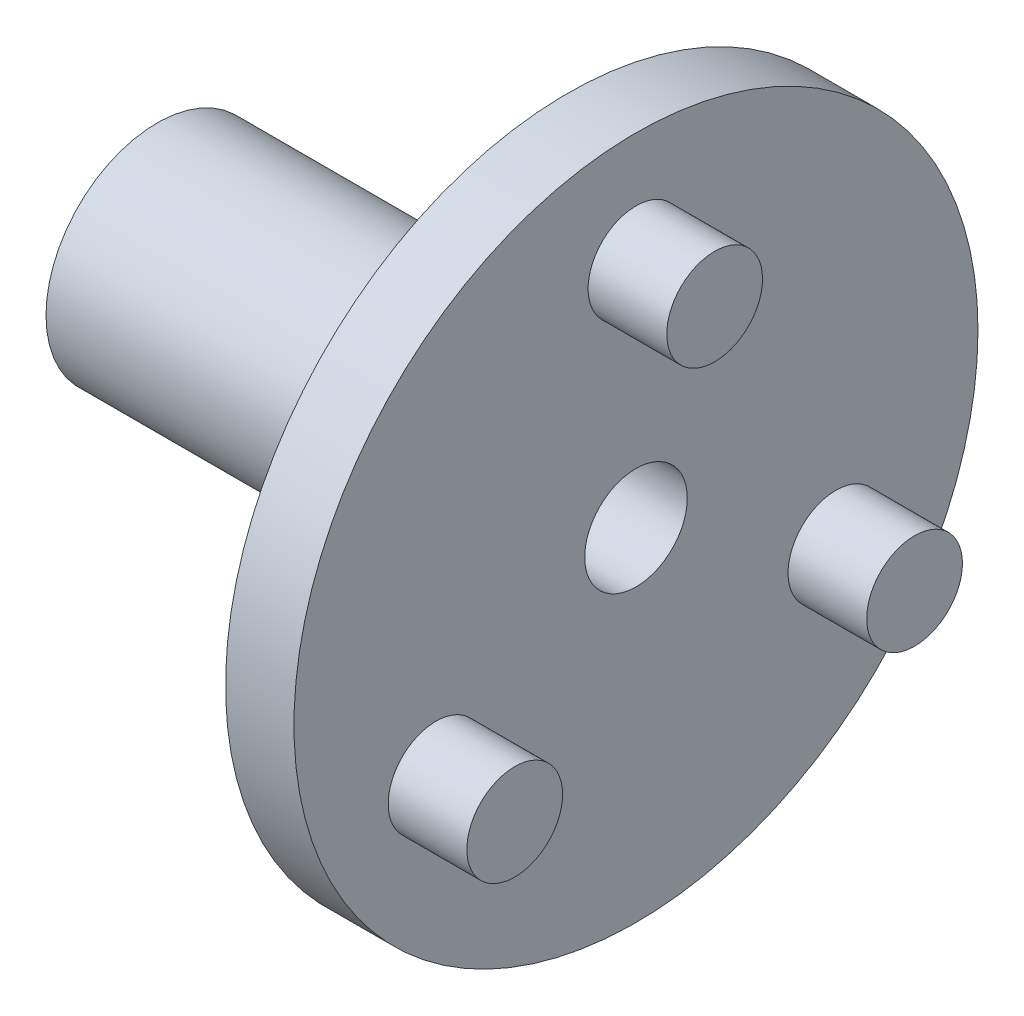
SolidWorks part; units mm, degrees
ref_plane "前视基准面" through (0, 0, 0) normal (0, 0, 1) x (1, 0, 0)
ref_plane "上视基准面" through (0, 0, 0) normal (0, 1, 0) x (1, 0, 0)
ref_plane "右视基准面" through (0, 0, 0) normal (1, 0, 0) x (0, 0, -1)
other "Configuration Table"
sketch "草图1" plane through (0, 0, 0) normal (1, 0, 0) x (0, 0, -1)
  circle A1 centre (0, 6.75) radius 1.4
  circle A2 centre (5.8457, -3.375) radius 1.4
  circle A3 centre (-5.8457, -3.375) radius 1.4
  point P10 (0, 0)
  dimension "D2" = 2.8
  dimension "D1" = 6.75
  dimension "D3" = 3
extrude "凸台-拉伸1" add sketch "草图1" along normal blind 2.3
sketch "草图2" plane through (0, 0, 0) normal (1, 0, 0) x (0, 0, -1)
  circle A0 centre (0, 0) radius 10
  circle A1 centre (0, 0) radius 1.5
  dimension "D1" = 20
  dimension "D2" = 3
extrude "凸台-拉伸2" add sketch "草图2" against normal blind 2
sketch "草图3" plane through (-2, 0, 0) normal (-1, 0, 0) x (0, 0, 1)
  circle A0 centre (0, 0) radius 5
  circle A1 centre (0, 0) radius 1.5
  dimension "D1" = 10
  dimension "D2" = 3
extrude "凸台-拉伸3" add sketch "草图3" along normal blind 4
sketch "草图4" plane through (-6, 0, 0) normal (-1, 0, 0) x (0, 0, 1)
  line L1 (-1.1587, 2.1587) -> (1.1587, 2.1587)
  line L2 (-1.1587, 2.1587) -> (-1.1587, -2.1587)
  line L3 (-1.1587, -2.1587) -> (1.1587, -2.1587)
  line L4 (1.1587, 2.1587) -> (1.1587, -2.1587)
  line L5 (-1.1587, 2.1587) -> (1.1587, -2.1587) construction
  line L6 (-1.1587, -2.1587) -> (1.1587, 2.1587) construction
  line L7 (2.1587, 1.1587) -> (-2.1587, 1.1587)
  line L8 (2.1587, 1.1587) -> (2.1587, -1.1587)
  line L9 (2.1587, -1.1587) -> (-2.1587, -1.1587)
  line L10 (-2.1587, 1.1587) -> (-2.1587, -1.1587)
  line L11 (2.1587, 1.1587) -> (-2.1587, -1.1587) construction
  line L12 (2.1587, -1.1587) -> (-2.1587, 1.1587) construction
  circle A0 centre (0, 0) radius 3.25
  circle A1 centre (0, 0) radius 2.45
  circle A2 centre (0, 0) radius 5
  point P12 (1.1587, -1.1587)
  circle M1 centre (0, 0) radius 5
  dimension "D1" = 6.5
  dimension "D2" = 4.9
  dimension "D4" = 10
  dimension "D3" = 1
extrude "凸台-拉伸4" add sketch "草图4" along normal blind 8 contours A0 | A1
extrude "凸台-拉伸5" add sketch "草图4<3>" along normal up to surface (8 mm away) contours L4 A1 L9 | L7 A1 L4 | L2 A1 L7 | L9 A1 L2 region at (-6, 1.5244, -1.5244) region at (-6, 1.5244, 1.5244) region at (-6, -1.5244, -1.5244) region at (-6, -1.5244, 1.5244) up to face at (-14, 0, 3.25)
sketch "草图4<3>" plane through (-6, 0, 0) normal (-1, 0, 0) x (0, 0, 1) same geometry as "草图4"
extrude "切除-拉伸1" cut sketch "草图4<6>" against normal blind 1 contours A0 M1 region at (-6, 0, -4.8586)
sketch "草图4<6>" plane through (-6, 0, 0) normal (-1, 0, 0) x (0, 0, 1) same geometry as "草图4"
